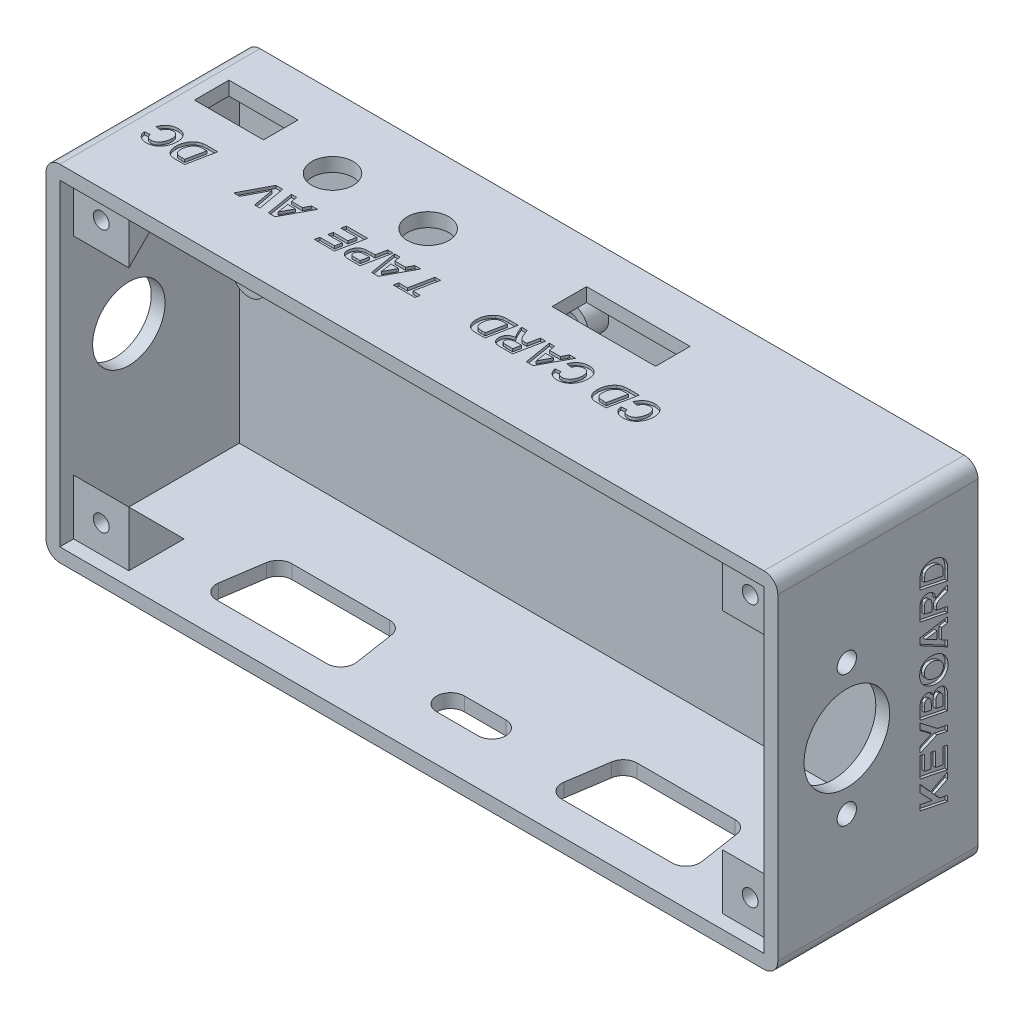
SolidWorks part; units mm, degrees
material "ABS"
ref_plane "Спереди" through (0, 0, 0) normal (0, 0, 1) x (1, 0, 0)
ref_plane "Сверху" through (0, 0, 0) normal (0, 1, 0) x (1, 0, 0)
ref_plane "Справа" through (0, 0, 0) normal (1, 0, 0) x (0, 0, -1)
sketch "Эскиз1" plane through (0, 0, 0) normal (0, 0, 1) x (1, 0, 0)
  line L1 (-53, -25) -> (53, -25)
  line L2 (-53, -25) -> (-53, 25)
  line L3 (-53, 25) -> (53, 25)
  line L4 (53, -25) -> (53, 25)
  line L5 (-53, -25) -> (53, 25) construction
  line L6 (-53, 25) -> (53, -25) construction
  point P0 (0, 0)
  dimension "D1" = 106
  dimension "D2" = 50
extrude "CaseBody" add sketch "Эскиз1" along normal blind 3
sketch "Эскиз2" plane through (0, 0, 3) normal (0, 0, 1) x (1, 0, 0)
  line L0 (53, 25) -> (-53, 25) construction
  line L1 (-51, -23) -> (51, -23)
  line L2 (-51, -23) -> (-51, 23)
  line L3 (-51, 23) -> (51, 23)
  line L4 (51, -23) -> (51, 23)
  line L5 (-51, -23) -> (51, 23) construction
  line L6 (-51, 23) -> (51, -23) construction
  line L7 (53, -25) -> (53, 25) construction
  line L9 (-53, -25) -> (53, -25)
  line L10 (-53, -25) -> (-53, 25)
  line L11 (-53, 25) -> (53, 25)
  line L12 (53, -25) -> (53, 25)
  line L13 (-53, -25) -> (53, 25) construction
  line L14 (-53, 25) -> (53, -25) construction
  point P0 (0, 0)
  point P10 (0, 0)
  dimension "D1" = 2
  dimension "D2" = 2
extrude "CaseBody2" add sketch "Эскиз2" along normal blind 26
sketch "Эскиз3" plane through (0, 0, 3) normal (0, 0, 1) x (1, 0, 0)
  line L0 (51, 23) -> (-51, 23) construction
  line L1 (-46.625, 1.53) -> (46.625, 1.53) construction
  line L2 (-46.625, 1.53) -> (-46.625, 19.18) construction
  line L3 (-46.625, 19.18) -> (46.625, 19.18) construction
  line L4 (46.625, 1.53) -> (46.625, 19.18) construction
  line L5 (-46.625, 1.53) -> (46.625, 19.18) construction
  line L6 (-46.625, 19.18) -> (46.625, 1.53) construction
  circle A0 centre (-46.625, 1.53) radius 2.5
  circle A1 centre (46.625, 1.53) radius 2.5
  circle A2 centre (0.005, 19.18) radius 2.5
  point P0 (0, 0)
  point P13 (0, 10.355)
  dimension "D4" = 5
  dimension "D1" = 93.25
  dimension "D2" = 17.65
  dimension "D3" = 46.63
  dimension "D5" = 3.82
extrude "SizifXXSFix" add sketch "Эскиз3" along normal blind 3
sketch "Эскиз4" plane through (0, 0, 6) normal (0, 0, 1) x (1, 0, 0)
  circle A0 centre (-46.625, 1.53) radius 1.2
  circle A1 centre (0.005, 19.18) radius 1.2
  circle A2 centre (46.625, 1.53) radius 1.2
  dimension "D1" = 2.4
extrude "Holes2_5" cut sketch "Эскиз4" against normal blind 5.6
sketch "Эскиз5" plane through (0, 25, 0) normal (0, 1, 0) x (1, 0, 0)
  line L1 (-49.3, -6.2) -> (-39.3, -6.2)
  line L2 (-49.3, -6.2) -> (-49.3, -11.2)
  line L3 (-49.3, -11.2) -> (-39.3, -11.2)
  line L4 (-39.3, -6.2) -> (-39.3, -11.2)
  line L5 (-49.3, -6.2) -> (-39.3, -11.2) construction
  line L6 (-49.3, -11.2) -> (-39.3, -6.2) construction
  line L7 (2.5, -6.2) -> (17.5, -6.2)
  line L8 (2.5, -6.2) -> (2.5, -11.2)
  line L9 (2.5, -11.2) -> (17.5, -11.2)
  line L10 (17.5, -6.2) -> (17.5, -11.2)
  line L11 (2.5, -6.2) -> (17.5, -11.2) construction
  line L12 (2.5, -11.2) -> (17.5, -6.2) construction
  line L13 (53, 0) -> (-53, 0) construction
  line L14 (-53, -29) -> (-53, 0) construction
  circle A0 centre (-30.1, -10.4) radius 3
  circle A1 centre (-16.25, -10.4) radius 3
  point P0 (-44.3, -8.7)
  point P9 (10, -8.7)
  dimension "D5" = 6
  dimension "D2" = 10
  dimension "D3" = 6.2
  dimension "D4" = 5
  dimension "D6" = 13.85
  dimension "D7" = 14.2
  dimension "D8" = 26.25
  dimension "D9" = 10.4
  dimension "D10" = 5
  dimension "D11" = 15
  dimension "D12" = 22.9
extrude "SizifXXS_Holes" cut sketch "Эскиз5" against normal up to next
sketch "Эскиз7" plane through (53, 0, 0) normal (1, 0, 0) x (0, 0, -1)
  line L0 (-20, 0) -> (-6.0564, 0) construction
  line L2 (0, -25) -> (0, 25) construction
  circle A0 centre (-19, 0) radius 6.2
  circle A1 centre (-19, -9.5) radius 1.4
  circle A2 centre (-19, 9.5) radius 1.4
  dimension "D1" = 12.4
  dimension "D4" = 2.8
  dimension "D2" = 19
  dimension "D3" = 19
extrude "PS2Hole" cut sketch "Эскиз7" against normal up to next
sketch "Эскиз8" plane through (51, 0, 0) normal (-1, 0, 0) x (0, 0, 1)
  line L0 (27, 23) -> (27, 15)
  line L1 (29, 23) -> (3, 23) construction
  line L2 (27, 15) -> (19, 23)
  line L3 (19, 23) -> (27, 23)
  line L4 (29, -23) -> (29, 23) construction
  dimension "D1" = 8
  dimension "D2" = 8
  dimension "D3" = 2
extrude "CaseTopFix" add sketch "Эскиз8" along normal blind 8
sketch "Эскиз9" plane through (0, 0, 27) normal (0, 0, 1) x (1, 0, 0)
  line L0 (43, 15) -> (43, 23) construction
  line L1 (43, 23) -> (51, 23) construction
  line L2 (43, 23) -> (43, 15) construction
  line L3 (43, 15) -> (51, 15) construction
  line L4 (51, 23) -> (51, 15) construction
  line L5 (43, 23) -> (51, 15) construction
  line L6 (43, 15) -> (51, 23) construction
  line L7 (43, 23) -> (51, 23) construction
  circle A0 centre (47, 19) radius 1.15
  point P0 (47, 19)
  dimension "D1" = 2.3
extrude "CaseTopHoles" cut sketch "Эскиз9" against normal up to next
mirror "CaseTopHoles1" about plane through (0, 0, 0) normal (0, 1, 0) of "CaseTopHoles", "CaseTopFix"
mirror "CaseTopHoles2" about plane through (0, 0, 0) normal (1, 0, 0) of "CaseTopHoles", "CaseTopHoles1", "CaseTopFix"
fillet "Fillet" radius 2 4 edges at (-53, 25, 14.5) (53, 25, 14.5) (53, -25, 14.5) (-53, -25, 14.5)
sketch "Эскиз10" plane through (0, 25, 0) normal (0, 1, 0) x (1, 0, 0)
  line L0 (51, 0) -> (-51, 0) construction
  line L1 (-53, -29) -> (-53, 0) construction
  text T0 "<r180>VA</r>" font "Times New Roman" height 4
  text T1 "<r180>EPAT</r>" font "Times New Roman" height 4
  text T2 "<r180>CD</r>" font "Times New Roman" height 4
  text T3 "<r180>DRAC DC</r>" font "Times New Roman" height 4
  dimension "D1" = 16
  dimension "D2" = 22.5962
  dimension "D3" = 11.2585
  dimension "D4" = 14.4528
  dimension "D5" = 21.8
extrude "InterfaceInfo" cut sketch "Эскиз10" against normal blind 0.4
sketch "Эскиз11" plane through (53, 0, 0) normal (1, 0, 0) x (0, 0, -1)
  line L0 (-4.4, -15.5) -> (-4.4, 15.5) construction
  line L1 (0, -23) -> (0, 23) construction
  text T0 "KEYBOARD" font "Arial" height 4
  point P0 (-4.4, 0)
  dimension "D1" = 4.4
  dimension "D2" = 31
extrude "PS2Info" cut sketch "Эскиз11" against normal blind 0.4
sketch "Эскиз12" plane through (0, 23, 0) normal (0, -1, 0) x (1, 0, 0)
  line L1 (-53, 0) -> (-53, 29) construction
  line L2 (-51, 0) -> (51, 0) construction
  text T0 "© Peter Ukhov 2023" font "Arial" height 6
  dimension "D1" = 16
  dimension "D2" = 14
sketch "Эскиз13" plane through (-53, 0, 0) normal (-1, 0, 0) x (0, 0, 1)
  line L1 (0, 23) -> (0, -23) construction
  circle A0 centre (19, 0) radius 5.25
  dimension "D1" = 10.5
  dimension "D2" = 19
extrude "ButtonHole" cut sketch "Эскиз13" against normal up to next
sketch "Эскиз14" plane through (-53, 0, 0) normal (-1, 0, 0) x (0, 0, 1)
  line L0 (6.2274, 10.1387) -> (6.2274, -12.1287) construction
  text T0 "POWER" font "Arial" height 4
extrude "ButtonInfo" cut sketch "Эскиз14" against normal blind 0.4
extrude "CopyLeft" cut sketch "Эскиз12" against normal blind 0.4
sketch "Эскиз15" plane through (0, -25, 0) normal (0, -1, 0) x (1, 0, 0)
  line L0 (-3, 20.4) -> (3, 20.4) construction
  line L1 (-3, 22.4) -> (3, 22.4)
  line L2 (-3, 18.4) -> (3, 18.4)
  line L3 (-51, 29) -> (51, 29) construction
  arc A0 (-3, 22.4) -> (-3, 18.4) centre (-3, 20.4) ccw
  arc A1 (3, 18.4) -> (3, 22.4) centre (3, 20.4) ccw
  point P2 (0, 20.4)
  dimension "D1" = 4
  dimension "D2" = 6
  dimension "D3" = 8.6
extrude "USBArduinoNano" cut sketch "Эскиз15" against normal up to next
sketch "Эскиз16" plane through (0, -25, 0) normal (0, -1, 0) x (1, 0, 0)
  line L0 (-34.9772, 22.0017) -> (-34.064, 16.0017)
  line L1 (-32.0868, 14.3026) -> (-17.9132, 14.3026)
  line L2 (-15.936, 16.0017) -> (-15.0228, 22.0017)
  line L3 (-17, 24.3026) -> (-33, 24.3026)
  line L4 (-33, 24.3026) -> (-17.9132, 14.3026) construction
  line L5 (-32.0868, 14.3026) -> (-17, 24.3026) construction
  line L6 (-51, 29) -> (51, 29) construction
  arc A0 (-15.0228, 22.0017) -> (-17, 24.3026) centre (-17, 22.3026) ccw
  arc A1 (-33, 24.3026) -> (-34.9772, 22.0017) centre (-33, 22.3026) ccw
  arc A2 (-17.9132, 14.3026) -> (-15.936, 16.0017) centre (-17.9132, 16.3026) ccw
  arc A3 (-34.064, 16.0017) -> (-32.0868, 14.3026) centre (-32.0868, 16.3026) ccw
  point P0 (-25, 19)
  dimension "D1" = 2
  dimension "D2" = 2
  dimension "D3" = 25
  dimension "D4" = 10
  dimension "D5" = 16
  dimension "D7" = 10
  dimension "D8" = 81.346
  dimension "D9" = 81.346
extrude "NESCut1" cut sketch "Эскиз16" against normal up to next
mirror "NESCut2" about plane through (0, 0, 0) normal (1, 0, 0) of "NESCut1"
equation "\"D1@Эскиз1\"=100+2*2+2"
equation "\"D5@Эскиз3\"=3.42+0.4"
equation "\"D2@Эскиз15\"=10-2-2"
equation "\"12ю5\"=12"
